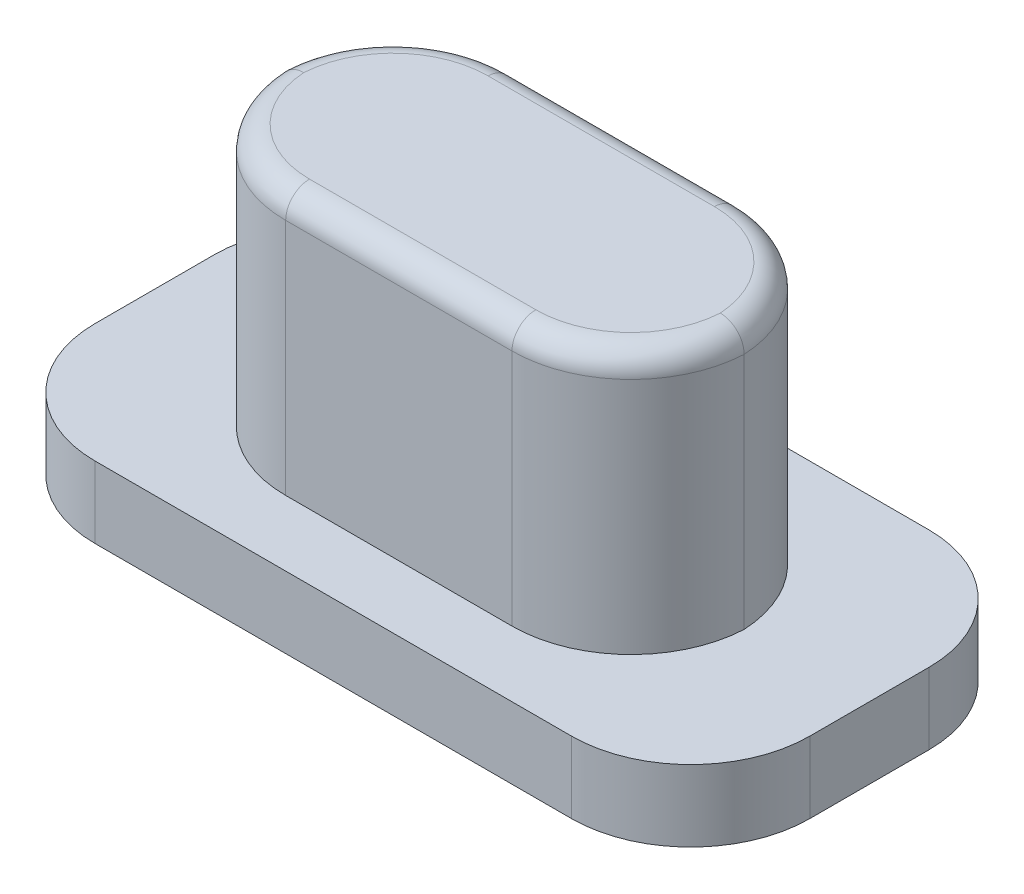
SolidWorks part; units mm, degrees
ref_plane "前视基准面" through (0, 0, 0) normal (0, 0, 1) x (1, 0, 0)
ref_plane "上视基准面" through (0, 0, 0) normal (0, 1, 0) x (1, 0, 0)
ref_plane "右视基准面" through (0, 0, 0) normal (1, 0, 0) x (0, 0, -1)
sketch "草图1" plane through (0, 0, 0) normal (0, 1, 0) x (1, 0, 0)
  line L1 (-2.5031, 1.7604) -> (3.4969, 1.7604)
  line L2 (-2.5031, 1.7604) -> (-2.5031, -1.2396)
  line L3 (-2.5031, -1.2396) -> (3.4969, -1.2396)
  line L4 (3.4969, 1.7604) -> (3.4969, -1.2396)
  dimension "D1" = 6
  dimension "D2" = 3
extrude "凸台-拉伸1" add sketch "草图1" along normal blind 0.6
sketch "草图2" plane through (0, 0.6, 0) normal (0, 1, 0) x (1, 0, 0)
  line L0 (3.4969, 1.7604) -> (-2.5031, 1.7604) construction
  line L1 (-1.4531, 1.2104) -> (2.4469, 1.2104)
  line L2 (-1.4531, 1.2104) -> (-1.4531, -0.6896)
  line L3 (-1.4531, -0.6896) -> (2.4469, -0.6896)
  line L4 (2.4469, 1.2104) -> (2.4469, -0.6896)
  line L5 (-1.4531, 1.2104) -> (2.4469, -0.6896) construction
  line L6 (-1.4531, -0.6896) -> (2.4469, 1.2104) construction
  line L7 (-2.5031, 1.7604) -> (-2.5031, -1.2396) construction
  point P0 (0.4969, 0.2604)
  point P8 (0.4969, 1.7604)
  point P12 (-2.5031, 0.2604)
  dimension "D1" = 3.9
  dimension "D2" = 1.9
extrude "凸台-拉伸2" add sketch "草图2" along normal blind 2.2
fillet "圆角1" radius 1 8 edges at (3.4969, 0.3, -1.7604) (3.4969, 0.3, 1.2396) (-2.5031, 0.3, -1.7604) (-2.5031, 0.3, 1.2396) (2.4469, 1.7, -1.2104) (-1.4531, 1.7, -1.2104) (-1.4531, 1.7, 0.6896) (2.4469, 1.7, 0.6896)
sketch "草图3" plane through (0, 0, 0) normal (0, -1, 0) x (-1, 0, 0)
  line L0 (1.5031, -1.2396) -> (-2.4969, -1.2396) construction
  line L1 (-1.9969, 1.0604) -> (1.0031, 1.0604)
  line L2 (-1.9969, 1.0604) -> (-1.9969, -0.5396)
  line L3 (-1.9969, -0.5396) -> (1.0031, -0.5396)
  line L4 (1.0031, 1.0604) -> (1.0031, -0.5396)
  line L5 (-1.9969, 1.0604) -> (1.0031, -0.5396) construction
  line L6 (-1.9969, -0.5396) -> (1.0031, 1.0604) construction
  line L7 (2.5031, 0.7604) -> (2.5031, -0.2396) construction
  point P0 (-0.4969, 0.2604)
  point P7 (-0.4969, -1.2396)
  point P11 (2.5031, 0.2604)
  dimension "D1" = 3
  dimension "D2" = 1.6
extrude "凸台-拉伸3" add sketch "草图3" along normal blind 0.2
fillet "圆角2" radius 0.2 6 edges at (2.1361, 2.8, -0.9349) (2.1361, 2.8, 0.4142) (0.4969, 2.8, 0.6896) (-1.1423, 2.8, 0.4142) (-1.1423, 2.8, -0.9349) (0.4969, 2.8, -1.2104)
